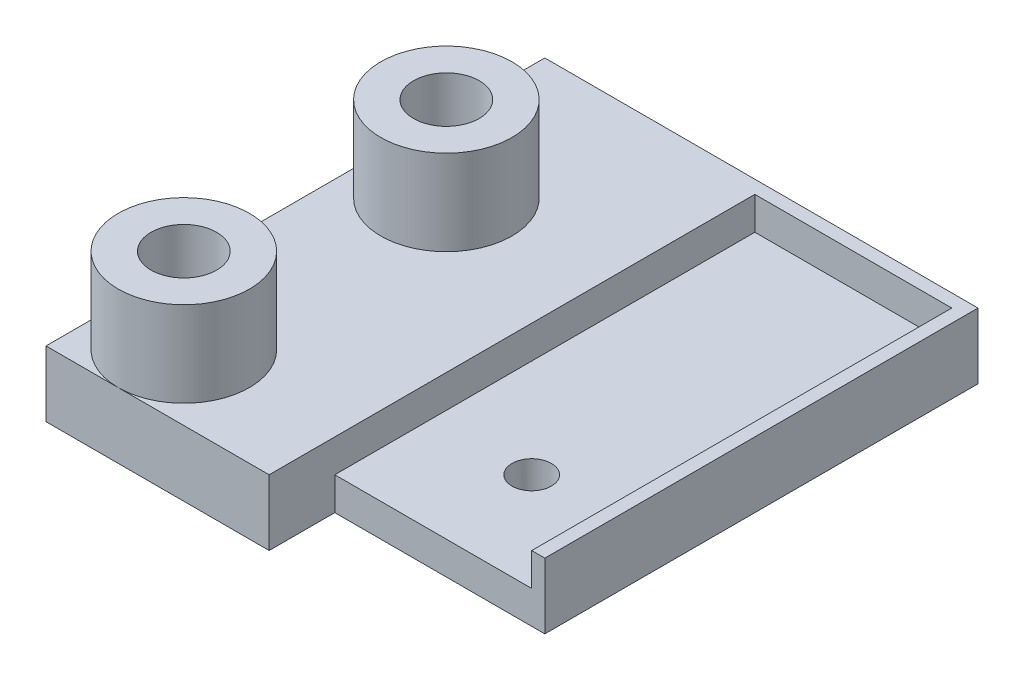
SolidWorks part; units mm, degrees
ref_plane "Front" through (0, 0, 0) normal (0, 0, 1) x (1, 0, 0)
ref_plane "Top" through (0, 0, 0) normal (0, 1, 0) x (1, 0, 0)
ref_plane "Right" through (0, 0, 0) normal (1, 0, 0) x (0, 0, -1)
sketch "Sketch1" plane through (0, 0, 0) normal (0, 1, 0) x (1, 0, 0)
  line L1 (0, 0) -> (-33, 0)
  line L2 (0, 0) -> (0, 33)
  line L3 (0, 33) -> (-33, 33)
  line L4 (-33, 0) -> (-33, 33)
  dimension "D1" = 33
  dimension "D2" = 33
extrude "Boss-Extrude1" add sketch "Sketch1" along normal blind 5
sketch "Sketch2" plane through (0, 5, 0) normal (0, 1, 0) x (1, 0, 0)
  line L0 (0, 0) -> (0, 33) construction
  line L1 (-1, 32) -> (-16, 32)
  line L2 (-1, 32) -> (-1, 0)
  line L3 (-1, 0) -> (-16, 0)
  line L4 (-16, 32) -> (-16, 0)
  line L5 (0, 33) -> (-33, 33) construction
  dimension "D1" = 1
  dimension "D2" = 15
  dimension "D3" = 32
  dimension "D4" = 1
extrude "Cut-Extrude1" cut sketch "Sketch2" against normal blind 2.5
sketch "Sketch4" plane through (0, 5, 0) normal (0, 1, 0) x (1, 0, 0)
  line L0 (-33, 33) -> (-33, 0) construction
  line L1 (-16, 0) -> (-33, 0)
  line L2 (-16, 0) -> (-16, -5)
  line L3 (-16, -5) -> (-33, -5)
  line L4 (-33, 0) -> (-33, -5)
  dimension "D1" = 5
extrude "Boss-Extrude3" add sketch "Sketch4" against normal up to surface (5 mm away) up to face at (-16.5, 0, -16.5)
sketch "Sketch3" plane through (0, 5, 0) normal (0, 1, 0) x (1, 0, 0)
  line L0 (-1, 32) -> (-16, 32) construction
  line L1 (-1, 32) -> (-16, 32) construction
  line L2 (-8.5, 32) -> (-8.5, 7.5) construction
  line L4 (-33, -5) -> (-16, -5) construction
  circle A0 centre (-8.5, 7.5) radius 1.5
  circle A1 centre (-27.5, 20) radius 2.5
  circle A2 centre (-27.5, 0) radius 2.5
  circle A3 centre (-27.5, 20) radius 5
  circle A4 centre (-27.5, 0) radius 5
  point P0 (-27.5, 20)
  point P3 (-8.5, 32)
  dimension "D4" = 3
  dimension "D5" = 5
  dimension "D1" = 19
  dimension "D2" = 12
  dimension "D3" = 24.5
  dimension "D6" = 20
extrude "Boss-Extrude4" add sketch "Sketch3" along normal blind 6.5 contours A3 A1 | A4 A2 region at (-32.3586, 5, -20) region at (-32.3586, 5, 0)
extrude "Cut-Extrude4" cut sketch "Sketch3<3>" against normal through all both and the other way through all contours A1 | A2 | A0 region at (-8.5, 5, -7.5) region at (-27.5, 5, -20) region at (-27.5, 5, 0)
sketch "Sketch3<3>" plane through (0, 5, 0) normal (0, 1, 0) x (1, 0, 0) same geometry as "Sketch3"
